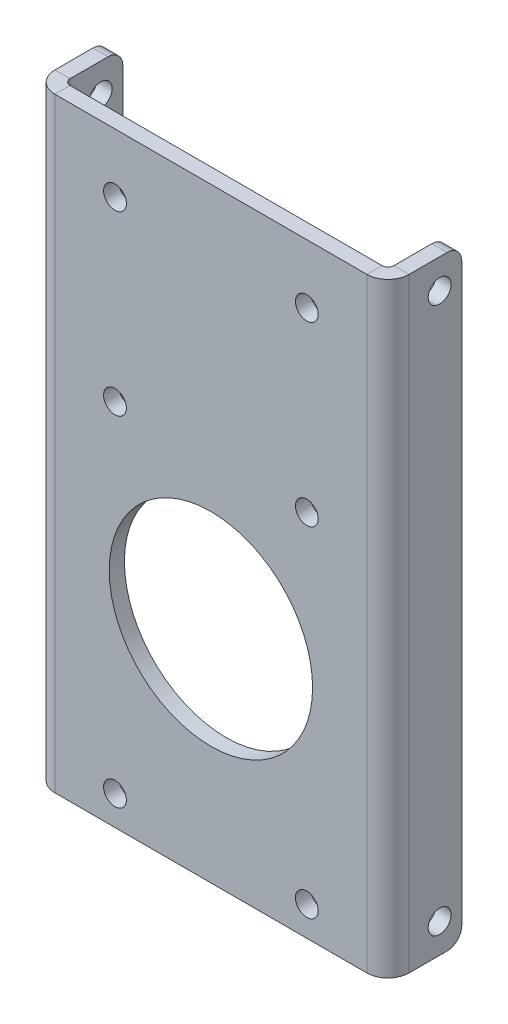
SolidWorks part; units mm, degrees
note: The reader was unsure of these and kept them because the rebuilt part matched: flange length of "Edge-Flange1".
material "5052-H32"
ref_plane "Front Plane" through (0, 0, 0) normal (0, 0, 1) x (1, 0, 0)
ref_plane "Top Plane" through (0, 0, 0) normal (0, 1, 0) x (1, 0, 0)
ref_plane "Right Plane" through (0, 0, 0) normal (1, 0, 0) x (0, 0, -1)
sketch "Sketch1" plane through (0, 0, 0) normal (0, 0, 1) x (1, 0, 0)
  line L0 (-38.1, 0) -> (38.1, 0) construction
  line L1 (-38.1, 82.8464) -> (38.1, 82.8464)
  line L2 (-38.1, 82.8464) -> (-38.1, -47.3286)
  line L3 (-38.1, -47.3286) -> (38.1, -47.3286)
  line L4 (38.1, 82.8464) -> (38.1, -47.3286)
  point P6 (0, 0)
  dimension "D1" = 47.3286
  dimension "D2" = 76.2
  dimension "D3" = 130.175
base flange "Base-Flange1" sketch "Sketch1" thickness 3.2639 reverse thickness direction no parameters "D1"=1.27
edge flange "Edge-Flange1" sketch "Sketch27" flange profiles "Sketch27", "Sketch28" flange angle 90 flange length 15.875 flange position material inside bend radius 1.27 thickness 3.2639 relief rectangular parameters "D6"=10, "D8"=0.254
sketch "Sketch27" plane through (38.1, 0, -3.2639) normal (-1, 0, 0) x (0, 1, 0)
  line L2 (-47.3286, 0) -> (-47.3286, 12.6111)
  line L3 (-47.3286, 12.6111) -> (82.8464, 12.6111)
  line L4 (82.8464, 12.6111) -> (82.8464, 0)
  line L5 (82.8464, 0) -> (-47.3286, 0) construction
  line L6 (82.8464, 0) -> (-47.3286, 0)
sketch "Sketch28" plane through (-38.1, 0, -3.2639) normal (1, 0, 0) x (0, -1, 0)
  line L0 (47.3286, 0) -> (-82.8464, 0) construction
  line L1 (47.3286, 0) -> (-82.8464, 0)
  line L2 (47.3286, 0) -> (47.3286, 12.6111)
  line L3 (47.3286, 12.6111) -> (-82.8464, 12.6111)
  line L4 (-82.8464, 12.6111) -> (-82.8464, 0)
bend "EdgeBend1" bend radius 1.27 bend angle 90 parameters "D5"=1
bend "EdgeBend2" bend radius 1.27 bend angle 90 parameters "D5"=2
sketch "Sketch29" plane through (38.1, 0, 0) normal (1, 0, 0) x (0, 0, -1)
  line L0 (11.1125, 76.4964) -> (11.1125, -40.9786) construction
  line L1 (15.875, -47.3286) -> (4.5339, -47.3286) construction
  line L2 (4.5339, 82.8464) -> (15.875, 82.8464) construction
  line L3 (0, -47.3286) -> (0, 82.8464) construction
  dimension "D1" = 6.35
  dimension "D2" = 6.35
  dimension "D3" = 11.1125
hole_wizard "#10 (0.1935) Diameter Hole1" positions "Sketch30" profile "Sketch31" hole size "#10" standard "ANSI Inch" end condition through all
sketch "Sketch30" plane through (38.1, 0, 0) normal (1, 0, 0) x (0, 0, -1)
  point P0 (11.1125, 76.4964)
  point P3 (11.1125, -40.9786)
sketch "Sketch31" plane through (38.1, 76.4964, -11.1125) normal (0, 1, 0) x (0, 0, -1)
  line L0 (0, 0) -> (0, 76.2)
  line L1 (0, 76.2) -> (2.4574, 76.2)
  line L2 (2.4574, 76.2) -> (2.4574, 0)
  line L5 (2.4574, 0) -> (0, 0)
  line L11 (0, -6.35) -> (0, 107.95) construction
  dimension "Thru Hole Dia." = 4.9149
  dimension "Thru Hole Depth" = 76.2
sketch "Sketch32" plane through (0, 0, -3.2639) normal (0, 0, -1) x (-1, 0, 0)
  circle A0 centre (0, 0) radius 21.8758
  dimension "D1" = 43.7515
extrude "Cut-Extrude1" cut sketch "Sketch32" against normal through all normal cut yes
sketch "Sketch33" plane through (0, 0, 0) normal (0, 0, 1) x (1, 0, 0)
  line L0 (-20.6375, -40.9786) -> (20.6375, -40.9786) construction
  line L1 (-38.1, -47.3286) -> (38.1, -47.3286) construction
  point P2 (0, -40.9786)
  dimension "D1" = 6.35
  dimension "D2" = 41.275
hole_wizard "#10 (0.1935) Diameter Hole2" positions "Sketch34" profile "Sketch35" hole size "#10" standard "ANSI Inch" end condition up to next
sketch "Sketch34" plane through (0, 0, 0) normal (0, 0, 1) x (1, 0, 0)
  point P0 (-20.6375, -40.9786)
  point P3 (20.6375, -40.9786)
sketch "Sketch35" plane through (-20.6375, -40.9786, 0) normal (1, 0, 0) x (0, -1, 0)
  line L0 (0, 0) -> (0, 3.2639)
  line L1 (0, 3.2639) -> (2.4574, 3.2639)
  line L2 (2.4574, 3.2639) -> (2.4574, 0)
  line L5 (2.4574, 0) -> (0, 0)
  line L11 (0, -6.35) -> (0, 107.95) construction
  dimension "Thru Hole Dia." = 4.9149
  dimension "Thru Hole Depth" = 3.2639
fillet "Fillet1" radius 3.175 4 edges at (-36.4681, 82.8464, -15.875) (36.4681, 82.8464, -15.875) (-36.4681, -47.3286, -15.875) (36.4681, -47.3286, -15.875)
sketch "Sketch36" plane through (0, 0, 0) normal (0, 0, 1) x (1, 0, 0)
  line L0 (-38.1, 82.8464) -> (38.1, 82.8464) construction
  point P0 (-20.6375, 32.0464)
  point P1 (20.6375, 32.0464)
  point P2 (20.6375, 70.1464)
  point P10 (-20.6375, 70.1464)
  dimension "D1" = 50.8
  dimension "D2" = 38.1
hole_wizard "#10 (0.1935) Diameter Hole3" positions "Sketch37" profile "Sketch38" hole size "#10" standard "ANSI Inch" end condition up to next
sketch "Sketch37" plane through (0, 0, 0) normal (0, 0, 1) x (1, 0, 0)
  point P0 (-20.6375, 70.1464)
  point P3 (20.6375, 70.1464)
  point P6 (20.6375, 32.0464)
  point P9 (-20.6375, 32.0464)
sketch "Sketch38" plane through (-20.6375, 70.1464, 0) normal (1, 0, 0) x (0, -1, 0)
  line L0 (0, 0) -> (0, 3.2639)
  line L1 (0, 3.2639) -> (2.4574, 3.2639)
  line L2 (2.4574, 3.2639) -> (2.4574, 0)
  line L5 (2.4574, 0) -> (0, 0)
  line L11 (0, -6.35) -> (0, 107.95) construction
  dimension "Thru Hole Dia." = 4.9149
  dimension "Thru Hole Depth" = 3.2639
sketch "Bend-Lines1" [suppressed] plane through (0, 0, 0) normal (0, 1, 0) x (1, 0, 0)
sketch "Bounding-Box1" [suppressed] plane through (0, 0, 0) normal (0, 1, 0) x (1, 0, 0)
sheet metal parameters "Sheet-Metal1" thickness 3.2639 parameters "D1"=1.27
flat pattern "Flat-Pattern1" [suppressed]
sketch "Bend-Lines2" plane through (0, 0, 0) normal (0, 1, 0) x (1, 0, 0)
sketch3d "Bounding-Box2" [suppressed]
  line L0 (38.1, 56.2696, 0) -> (38.1, -45.3304, 0) construction
  line L1 (-38.1, 56.2696, 0) -> (-38.1, -45.3304, 0) construction
  line L2 (38.1, 56.2696, 0) -> (-38.1, 56.2696, 0) construction
  line L3 (38.1, -45.3304, 0) -> (-38.1, -45.3304, 0) construction
sheet metal parameters "Sheet-Metal8" thickness 3.2639 parameters "D1"=1.27
flat pattern "Flat-Pattern1"
sketch "Bend-Lines2" plane through (0, 0, 0) normal (0, 0, 1) x (1, 0, 0)
  line L0 (-35.8453, 56.2696) -> (-35.8453, -45.3304) construction
  line L1 (35.8453, -45.3304) -> (35.8453, 56.2696) construction
  line L2 (-35.8453, 56.2696) -> (-35.8453, -45.3304) construction
  line L3 (35.8453, -45.3304) -> (35.8453, 56.2696) construction
sketch3d "Bounding-Box2" [suppressed]
  line L0 (49.4656, 56.2696, 0) -> (49.4656, -45.3304, 0) construction
  line L1 (-49.4656, 56.2696, 0) -> (-49.4656, -45.3304, 0) construction
  line L2 (49.4656, 56.2696, 0) -> (-49.4656, 56.2696, 0) construction
  line L3 (49.4656, -45.3304, 0) -> (-49.4656, -45.3304, 0) construction
bend of the flat pattern "Flatten-<EdgeBend1>1"
bend of the flat pattern "Flatten-<EdgeBend2>1"
sheet metal parameters "Sheet-Metal9" thickness 3.2639 parameters "D1"=1.27
flat pattern "Flat-Pattern1" [suppressed]
sketch "Bend-Lines2" plane through (0, 0, 0) normal (0, 0, 1) x (1, 0, 0)
  line L0 (-35.8453, 56.2696) -> (-35.8453, -45.3304) construction
  line L1 (35.8453, -45.3304) -> (35.8453, 56.2696) construction
  line L2 (-35.8453, 56.2696) -> (-35.8453, -45.3304) construction
  line L3 (35.8453, -45.3304) -> (35.8453, 56.2696) construction
sketch3d "Bounding-Box2" [suppressed]
  line L0 (49.4656, 56.2696, 0) -> (49.4656, -45.3304, 0) construction
  line L1 (-49.4656, 56.2696, 0) -> (-49.4656, -45.3304, 0) construction
  line L2 (49.4656, 56.2696, 0) -> (-49.4656, 56.2696, 0) construction
  line L3 (49.4656, -45.3304, 0) -> (-49.4656, -45.3304, 0) construction
bend of the flat pattern "Flatten-<EdgeBend1>1"
bend of the flat pattern "Flatten-<EdgeBend2>1"
sketch "Sketch29-1" [suppressed] plane through (33.5906, 0, 0) normal (0, 0, 1) x (1, 0, 0)
  line L0 (11.1125, 49.9196) -> (11.1125, -38.9804) construction
  line L1 (15.875, -45.3304) -> (-83.0561, -45.3304) construction
  line L2 (-83.0561, 56.2696) -> (15.875, 56.2696) construction
  line L3 (0, -45.3304) -> (0, 56.2696) construction
  dimension "D1" = 6.35
  dimension "D2" = 6.35
  dimension "D3" = 11.1125
sheet metal parameters "Sheet-Metal10" thickness 3.2639 parameters "D1"=1.27
flat pattern "Flat-Pattern1" [suppressed]
sketch "Bend-Lines2" plane through (0, 0, 0) normal (0, 0, 1) x (1, 0, 0)
  line L0 (-35.8453, 82.8464) -> (-35.8453, -47.3286) construction
  line L1 (35.8453, -47.3286) -> (35.8453, 82.8464) construction
  line L2 (-35.8453, 82.8464) -> (-35.8453, -47.3286) construction
  line L3 (35.8453, -47.3286) -> (35.8453, 82.8464) construction
sketch3d "Bounding-Box2" [suppressed]
  line L0 (49.4656, 82.8464, 0) -> (49.4656, -47.3286, 0) construction
  line L1 (-49.4656, 82.8464, 0) -> (-49.4656, -47.3286, 0) construction
  line L2 (49.4656, 82.8464, 0) -> (-49.4656, 82.8464, 0) construction
  line L3 (49.4656, -47.3286, 0) -> (-49.4656, -47.3286, 0) construction
bend of the flat pattern "Flatten-<EdgeBend1>1"
bend of the flat pattern "Flatten-<EdgeBend2>1"
sketch "Sketch29-1" [suppressed] plane through (33.5906, 0, 0) normal (0, 0, 1) x (1, 0, 0)
  line L0 (11.1125, 76.4964) -> (11.1125, -40.9786) construction
  line L1 (15.875, -47.3286) -> (-83.0561, -47.3286) construction
  line L2 (-83.0561, 82.8464) -> (15.875, 82.8464) construction
  line L3 (0, -47.3286) -> (0, 82.8464) construction
  dimension "D1" = 6.35
  dimension "D2" = 6.35
  dimension "D3" = 11.1125
sheet metal parameters "Sheet-Metal11" thickness 3.2639 parameters "D1"=1.27
flat pattern "Flat-Pattern1" [suppressed]
sketch "Bend-Lines2" plane through (0, 0, 0) normal (0, 0, 1) x (1, 0, 0)
  line L0 (-35.8453, 82.8464) -> (-35.8453, -47.3286) construction
  line L1 (35.8453, -47.3286) -> (35.8453, 82.8464) construction
  line L2 (-35.8453, 82.8464) -> (-35.8453, -47.3286) construction
  line L3 (35.8453, -47.3286) -> (35.8453, 82.8464) construction
sketch3d "Bounding-Box2" [suppressed]
  line L0 (49.4654, -47.3286, 0) -> (49.4656, 82.8464, 0) construction
  line L1 (-49.4656, -47.3285, 0) -> (-49.4654, 82.8465, 0) construction
  line L2 (49.4654, -47.3286, 0) -> (-49.4656, -47.3285, 0) construction
  line L3 (49.4656, 82.8464, 0) -> (-49.4654, 82.8465, 0) construction
bend of the flat pattern "Flatten-<EdgeBend1>1"
bend of the flat pattern "Flatten-<EdgeBend2>1"
sketch "Sketch29-1" [suppressed] plane through (33.5906, 0, 0) normal (0, 0, 1) x (1, 0, 0)
  line L0 (11.1125, 76.4964) -> (11.1125, -40.9786) construction
  line L1 (12.7, -47.3286) -> (-79.8811, -47.3286) construction
  line L2 (-79.8811, 82.8464) -> (12.7, 82.8464) construction
  line L3 (0, -47.3286) -> (0, 82.8464) construction
  dimension "D1" = 6.35
  dimension "D2" = 6.35
  dimension "D3" = 11.1125
sheet metal parameters "Sheet-Metal12" thickness 3.2639 parameters "D1"=1.27
flat pattern "Flat-Pattern1" [suppressed]
sketch "Bend-Lines2" plane through (0, 0, 0) normal (0, 0, 1) x (1, 0, 0)
  line L0 (-35.8453, 82.8464) -> (-35.8453, -47.3286) construction
  line L1 (35.8453, -47.3286) -> (35.8453, 82.8464) construction
  line L2 (-35.8453, 82.8464) -> (-35.8453, -47.3286) construction
  line L3 (35.8453, -47.3286) -> (35.8453, 82.8464) construction
sketch3d "Bounding-Box2" [suppressed]
  line L0 (49.4654, -47.3286, 0) -> (49.4656, 82.8464, 0) construction
  line L1 (-49.4656, -47.3285, 0) -> (-49.4654, 82.8465, 0) construction
  line L2 (49.4654, -47.3286, 0) -> (-49.4656, -47.3285, 0) construction
  line L3 (49.4656, 82.8464, 0) -> (-49.4654, 82.8465, 0) construction
bend of the flat pattern "Flatten-<EdgeBend1>1"
bend of the flat pattern "Flatten-<EdgeBend2>1"
sketch "Sketch29-1" [suppressed] plane through (33.5906, 0, 0) normal (0, 0, 1) x (1, 0, 0)
  line L0 (11.1125, 76.4964) -> (11.1125, -40.9786) construction
  line L1 (12.7, -47.3286) -> (-79.8811, -47.3286) construction
  line L2 (-79.8811, 82.8464) -> (12.7, 82.8464) construction
  line L3 (0, -47.3286) -> (0, 82.8464) construction
  dimension "D1" = 6.35
  dimension "D2" = 6.35
  dimension "D3" = 11.1125
